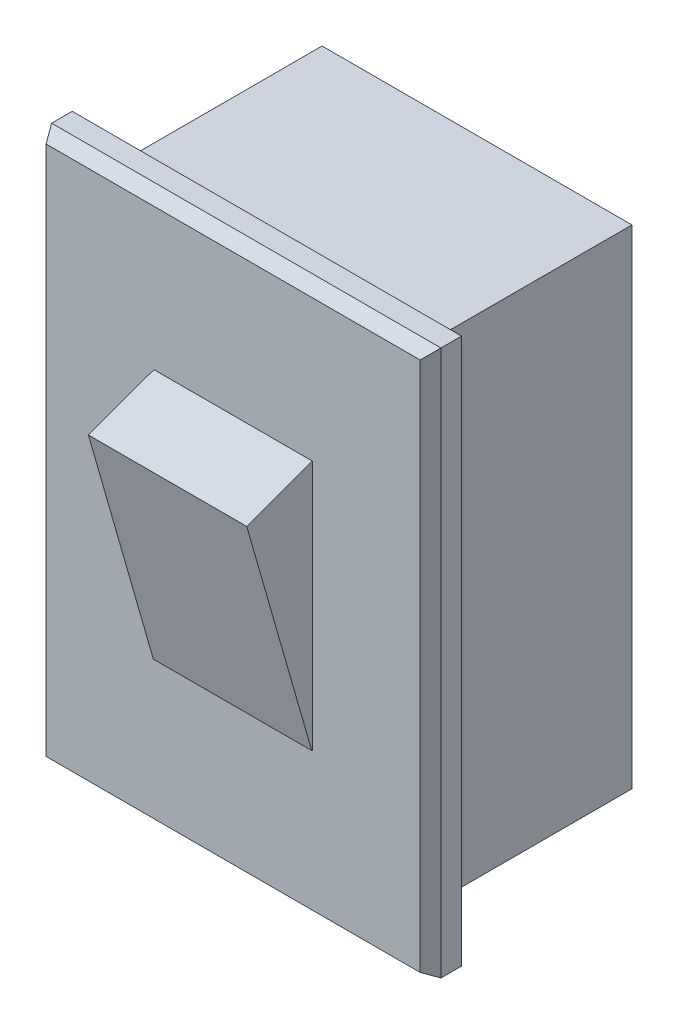
SolidWorks part; units mm, degrees
ref_plane "前视基准面" through (0, 0, 0) normal (0, 0, 1) x (1, 0, 0)
ref_plane "上视基准面" through (0, 0, 0) normal (0, 1, 0) x (1, 0, 0)
ref_plane "右视基准面" through (0, 0, 0) normal (1, 0, 0) x (0, 0, -1)
sketch "草图1" plane through (0, 0, 0) normal (0, 0, 1) x (1, 0, 0)
  line L1 (7.375, -10.335) -> (-7.375, -10.335)
  line L2 (7.375, -10.335) -> (7.375, 10.335)
  line L3 (7.375, 10.335) -> (-7.375, 10.335)
  line L4 (-7.375, -10.335) -> (-7.375, 10.335)
  line L5 (7.375, -10.335) -> (-7.375, 10.335) construction
  line L6 (7.375, 10.335) -> (-7.375, -10.335) construction
  point P0 (0, 0)
  dimension "D1" = 14.75
  dimension "D2" = 20.67
extrude "凸台-拉伸1" add sketch "草图1" along normal blind 1.28
ref_plane "基准面1" through (0, 0, 1.28) normal (0, 0, 1) x (1, 0, 0)
sketch "草图2" plane through (0, 0, 1.28) normal (0, 0, 1) x (1, 0, 0)
  line L2 (0, -4.8) -> (-3, -4.8)
  line L3 (0, -4.8) -> (3, -4.8)
  line L4 (3, -4.8) -> (3, 4.8)
  line L5 (3, 4.8) -> (-3, 4.8)
  line L6 (-3, 4.8) -> (-3, -4.8)
extrude "凸台-拉伸2" add sketch "草图2" along normal blind 3
chamfer "倒角3" distance 2 angle 80 1 edges at (0, -4.8, 4.28) first distance on face at (0, -4.8, 2.78)
chamfer "倒角4" distance 0.5 angle 30 4 edges at (0, 10.335, 1.28) (0, -10.335, 1.28) (7.375, 0, 1.28) (-7.375, 0, 1.28) first distance on face at (0, 10.335, 0.64) first distance on face at (0, -10.335, 0.64) first distance on face at (7.375, 0, 0.64) first distance on face at (-7.375, 0, 0.64)
chamfer "倒角5" distance 3 angle 20 1 edges at (0, 4.8, 3.9727) first distance on face at (0, 4.8, 2.6264)
chamfer "倒角6" distance 9 angle 6 1 edges at (0, -4.8, 2.28) first distance on face at (0, -0.513, 3.0359)
ref_plane "基准面2" through (0, 0, 0) normal (0, 0, -1) x (-1, 0, 0)
sketch "草图3" plane through (0, 0, 0) normal (0, 0, -1) x (-1, 0, 0)
  line L1 (5.87, -9.25) -> (-5.87, -9.25)
  line L2 (5.87, -9.25) -> (5.87, 9.25)
  line L3 (5.87, 9.25) -> (-5.87, 9.25)
  line L4 (-5.87, -9.25) -> (-5.87, 9.25)
  line L5 (5.87, -9.25) -> (-5.87, 9.25) construction
  line L6 (5.87, 9.25) -> (-5.87, -9.25) construction
  point P0 (0, 0)
  dimension "D1" = 11.74
  dimension "D2" = 18.5
extrude "凸台-拉伸3" add sketch "草图3" along normal blind 7.96
